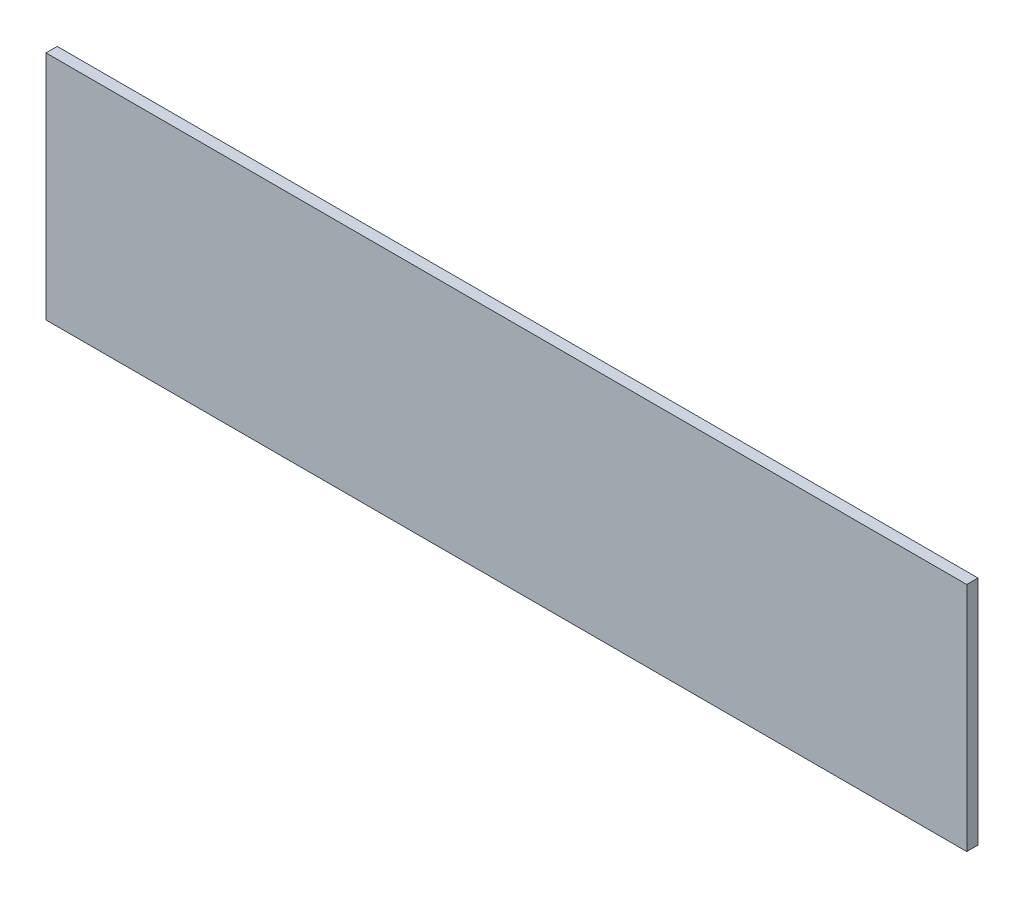
SolidWorks part; units mm, degrees
material "아크릴(내충격성)"
ref_plane "정면" through (0, 0, 0) normal (0, 0, 1) x (1, 0, 0)
ref_plane "윗면" through (0, 0, 0) normal (0, 1, 0) x (1, 0, 0)
ref_plane "우측면" through (0, 0, 0) normal (1, 0, 0) x (0, 0, -1)
sketch "스케치1" plane through (0, 0, 0) normal (0, 0, 1) x (1, 0, 0)
  line L1 (205, 51.5) -> (-205, 51.5)
  line L2 (205, 51.5) -> (205, -51.5)
  line L3 (205, -51.5) -> (-205, -51.5)
  line L4 (-205, 51.5) -> (-205, -51.5)
  line L5 (205, 51.5) -> (-205, -51.5) construction
  line L6 (205, -51.5) -> (-205, 51.5) construction
  point P0 (0, 0)
  dimension "D1" = 103
  dimension "D2" = 410
extrude "보스-돌출1" add sketch "스케치1" along normal blind 5
